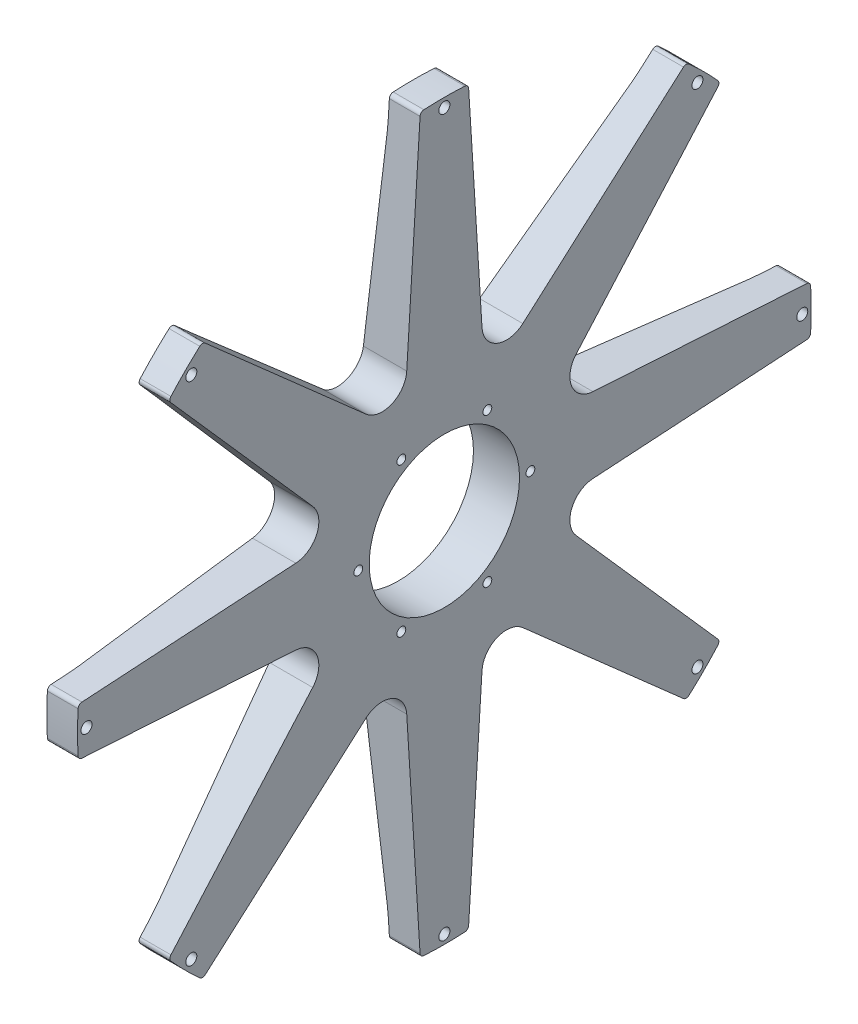
SolidWorks part; units mm, degrees
material "6061-T6 (SS)"
ref_plane "Front Plane" through (0, 0, 0) normal (1, 0, 0) x (0, 1, 0)
ref_plane "Top Plane" through (0, 0, 0) normal (0, 0, 1) x (0, 1, 0)
ref_plane "Right Plane" through (0, 0, 0) normal (0, 1, 0) x (-1, 0, 0)
sketch "Rim Base" plane through (1321.9127, 0, 0) normal (-1, 0, 0) x (0, -1, 0)
  line L0 (-601.9127, 917.067) -> (-621.8122, 869.0252) construction
  line L1 (-601.9127, 742.367) -> (-601.9127, 737.992)
  line L2 (-601.9127, 737.992) -> (-601.9127, 737.592) construction
  line L3 (-601.9127, 917.067) -> (-582.0132, 869.0252) construction
  line L4 (-601.9127, 917.067) -> (-601.9127, 742.367)
  line L5 (-621.8122, 869.0252) -> (-606.8221, 747.1987)
  line L6 (-601.9127, 742.367) -> (-589.9127, 742.367) construction
  line L7 (-607.2191, 747.1498) -> (-606.8221, 747.1987) construction
  line L8 (-601.9127, 917.067) -> (-601.9127, 969.067)
  line L9 (-590.0514, 740.1425) -> (-582.0132, 869.0252)
  line L10 (-582.0132, 869.0252) -> (-587.2177, 738.1946) construction
  circle A0 centre (-601.9127, 742.367) radius 2.6892
  circle A1 centre (-601.9127, 742.367) radius 2.4892 construction
  circle A2 centre (-601.9127, 742.367) radius 4.375
  arc A3 (-616.6077, 738.1946) -> (-587.2177, 738.1946) centre (-601.9127, 917.067) ccw construction
  arc A4 (-616.6077, 738.1946) -> (-587.2177, 738.1946) centre (-601.9127, 917.067) ccw construction
  circle A5 centre (-601.9127, 1091.767) radius 2.4892 construction
  circle A6 centre (-601.9127, 1091.767) radius 2.4892
  circle A7 centre (-601.9127, 917.067) radius 36.7
  circle A8 centre (-601.9127, 917.067) radius 36.5 construction
  circle A9 centre (-601.9127, 917.067) radius 36.5 construction
  circle A10 centre (-601.9127, 917.067) radius 36.5
  circle A11 centre (-601.9127, 917.067) radius 52
  arc A12 (-557.9844, 944.8934) -> (-599.7785, 969.0232) centre (-601.9127, 917.067) ccw construction
  arc A13 (-606.8221, 747.1987) -> (-606.2707, 741.9818) centre (-758.7804, 728.5009) cw
  arc A14 (-590.0514, 740.1425) -> (-591.9361, 738.2701) centre (-592.0476, 740.267) cw
  arc A15 (-601.9127, 737.992) -> (-591.9361, 738.2701) centre (-601.9127, 917.067) ccw
  circle A16 centre (-638.2858, 938.067) radius 2.1526 construction
  circle A17 centre (-638.2858, 896.067) radius 2.1527 construction
  circle A18 centre (-601.9127, 875.067) radius 2.1526 construction
  circle A19 centre (-565.5396, 896.067) radius 2.1526 construction
  circle A20 centre (-565.5396, 938.067) radius 2.1527 construction
  circle A21 centre (-601.9127, 959.067) radius 2.1526 construction
  circle A22 centre (-638.2858, 938.067) radius 2.1526
  circle A23 centre (-638.2858, 896.067) radius 2.1527
  circle A24 centre (-601.9127, 875.067) radius 2.1526
  circle A25 centre (-565.5396, 896.067) radius 2.1526
  circle A26 centre (-565.5396, 938.067) radius 2.1527
  circle A27 centre (-601.9127, 959.067) radius 2.1526
  arc M9 (-592.0897, 747.351) -> (-611.7357, 747.351) centre (-601.9127, 917.067) cw
  dimension "D1" = 0.2
  dimension "D2" = 0.4
  dimension "D3" = 0.2
  dimension "D4" = 12
  dimension "D7" = 2
  dimension "D5" = 22.5
  dimension "D6" = 0.4
extrude "Boss-Extrude1" add sketch "Rim Base" along normal blind 22.5 contours A11 L4 M9 | L4 A11 L8 A7 | L1 A2 L4 A0 | L4 A2 M9 | L8 A27 | A26 | L4 A24 | A25 region at (1321.9127, 599.942, 740.3962) region at (1321.9127, 593.722, 808.6866) region at (1321.9127, 600.7499, 868.9906) region at (1321.9127, 600.9991, 875.067) region at (1321.9127, 600.9991, 959.067) region at (1321.9127, 565.5396, 896.067) region at (1321.9127, 565.5396, 938.067)
ref_axis "Axis1" through (1299.4127, 601.9127, 917.067) along (1, 0, 0)
ref_axis "Axis2" through (1299.4127, 601.9127, 742.367) along (1, 0, 0)
ref_plane "Plane1" through (0, 601.9127, 0) normal (0, 1, 0) x (1, 0, 0)
sketch "Sketch1" plane through (0, 601.9127, 0) normal (0, 1, 0) x (1, 0, 0)
  line L0 (1321.9127, -865.067) -> (1299.4127, -865.067)
  line L1 (1299.4127, -880.367) -> (1299.4127, -745.0562) construction
  line L2 (1299.4127, -880.367) -> (1299.4127, -745.0562)
  line L6 (1299.4127, -739.6778) -> (1299.4127, -745.0562) construction
  line L7 (1306.9127, -737.992) -> (1306.9127, -747.992)
  line L9 (1306.733, -753.351) -> (1299.5924, -859.708)
  line L12 (1299.4127, -739.6778) -> (1299.4127, -737.992) construction
  line L13 (1299.4127, -737.992) -> (1321.9127, -737.992) construction
  line L15 (1299.4127, -739.6778) -> (1299.4127, -745.0562)
  line L16 (1299.4127, -739.6778) -> (1299.4127, -737.992)
  line L17 (1299.4127, -737.992) -> (1321.9127, -737.992)
  line L18 (1321.9127, -739.6778) -> (1321.9127, -737.992) construction
  arc A0 (1306.9127, -747.992) -> (1306.733, -753.351) centre (1226.9127, -747.992) cw
  arc A1 (1299.5924, -859.708) -> (1299.4127, -865.067) centre (1379.4127, -865.067) ccw
  dimension "D3" = 80
  dimension "D1" = 15
  dimension "D2" = 10
revolve "Cut-Revolve1" cut sketch "Sketch1" angle 360 about axis through (1299.4127, 601.9127, 917.067) along (1, 0, 0) region at (1302.1429, 601.9127, 779.8647)
mirror "Mirror1" about plane through (1299.4127, 601.9127, 0) normal (0, -1, 0) of bodies 104
pattern_circular "CirPattern1" count 8 every 45 about axis through (1299.4127, 601.9127, 917.067) along (1, 0, 0) of bodies 113 104
combine bodies "Combine1" bodies to combine 113 106 107 108 109 110 111 112
extrude "Cut-Extrude1" cut sketch "Rim Base<4>" along normal through all contours L8 A27 | L8 A27 | A26 | A25 | L4 A24 | L4 A24 | A23 | A22 region at (1321.9127, 602.8263, 875.067) region at (1321.9127, 600.9991, 875.067) region at (1321.9127, 600.9991, 959.067) region at (1321.9127, 602.8263, 959.067) region at (1321.9127, 638.2858, 938.067) region at (1321.9127, 638.2858, 896.067) region at (1321.9127, 565.5396, 896.067) region at (1321.9127, 565.5396, 938.067)
sketch "Rim Base<4>" plane through (1321.9127, 0, 0) normal (-1, 0, 0) x (0, -1, 0) same geometry as "Rim Base"
fillet "Fillet2" radius 12 8 edges at (1310.6627, 582.0132, 965.1087) (1310.6627, 553.871, 936.9665) (1310.6627, 553.871, 897.1674) (1310.6627, 582.0132, 869.0252) (1310.6627, 621.8122, 869.0252) (1310.6627, 649.9544, 897.1674) (1310.6627, 649.9544, 936.9665) (1310.6627, 621.8122, 965.1087)
equation "\"tol\"= 0.2mm"
